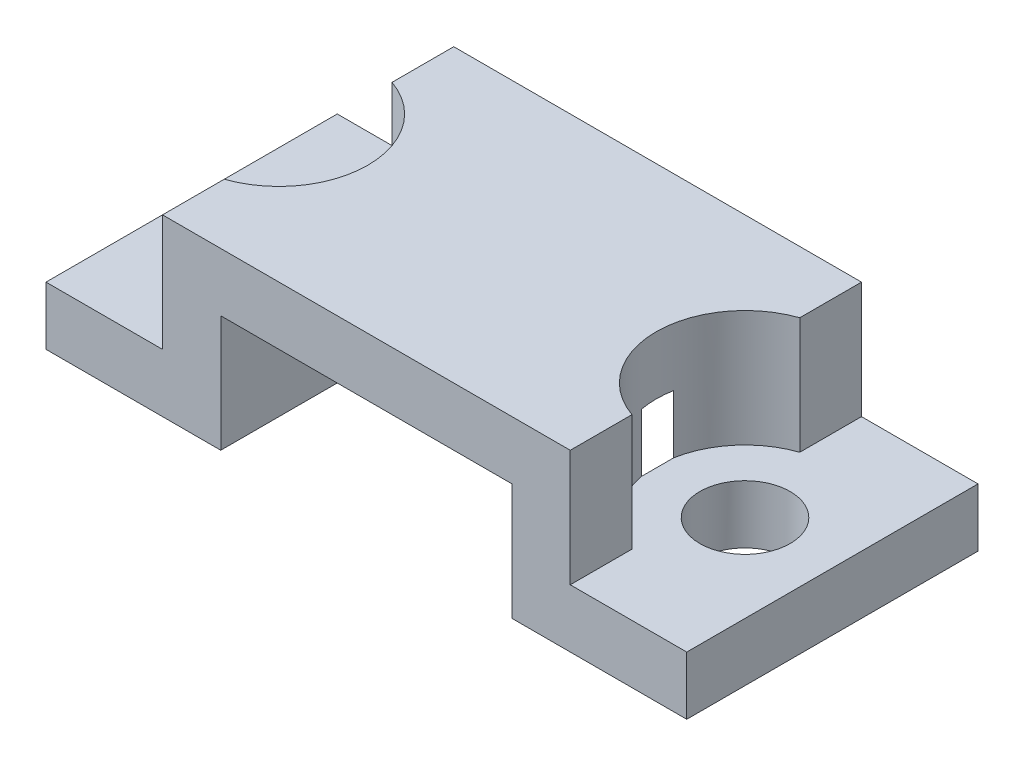
SolidWorks part; units mm, degrees
ref_plane "前视基准面" through (0, 0, 0) normal (0, 0, 1) x (1, 0, 0)
ref_plane "上视基准面" through (0, 0, 0) normal (0, 1, 0) x (1, 0, 0)
ref_plane "右视基准面" through (0, 0, 0) normal (1, 0, 0) x (0, 0, -1)
sketch "草图1" plane through (0, 0, 0) normal (0, 1, 0) x (1, 0, 0)
  line L1 (-11, -5) -> (11, -5)
  line L2 (-11, -5) -> (-11, 5)
  line L3 (-11, 5) -> (11, 5)
  line L4 (11, -5) -> (11, 5)
  line L5 (-11, -5) -> (11, 5) construction
  line L6 (-11, 5) -> (11, -5) construction
  point P0 (0, 0)
  dimension "D1" = 10
  dimension "D2" = 22
extrude "凸台-拉伸1" add sketch "草图1" along normal blind 6
sketch "草图2" plane through (0, 0, 5) normal (0, 0, 1) x (1, 0, 0)
  line L1 (-5, 0) -> (5, 0)
  line L2 (-5, 0) -> (-5, 4)
  line L3 (-5, 4) -> (5, 4)
  line L4 (-11, 0) -> (11, 0)
  line L5 (11, 0) -> (11, 6)
  line L6 (11, 6) -> (-11, 6)
  line L7 (-11, 6) -> (-11, 0)
  line L8 (-11, 0) -> (11, 0)
  line L9 (11, 0) -> (11, 6)
  line L10 (11, 6) -> (-11, 6)
  line L11 (-11, 6) -> (-11, 0)
  line L12 (5, 0) -> (5, 4)
  line L13 (-11, 0) -> (-5, 0)
  line L14 (-11, 0) -> (-11, 2)
  line L15 (-11, 2) -> (-5, 2)
  line L16 (-5, 0) -> (-5, 2)
  line L17 (11, 0) -> (5, 0)
  line L18 (11, 0) -> (11, 2)
  line L19 (11, 2) -> (5, 2)
  line L20 (5, 0) -> (5, 2)
  line L21 (-11, 6) -> (-7, 6)
  line L22 (-11, 6) -> (-11, 2)
  line L23 (-11, 2) -> (-7, 2)
  line L24 (-7, 6) -> (-7, 2)
  line L25 (11, 6) -> (7, 6)
  line L26 (11, 6) -> (11, 2)
  line L27 (11, 2) -> (7, 2)
  line L28 (7, 6) -> (7, 2)
  line M13 (-11, 0) -> (11, 0)
  line M15 (11, 6) -> (-11, 6)
  line M16 (-11, 6) -> (-11, 0)
  dimension "D2" = 10
  dimension "D3" = 6
  dimension "D4" = 2
  dimension "D5" = 2
  dimension "D6" = 2
  dimension "D7" = 2
  dimension "D8" = 2
  dimension "D1" = 0
extrude "切除-拉伸1" cut sketch "草图2" against normal blind 24 contours L24 L10 L15 M16 | L28 L19 L9 M15 | L12 L3 L2 M13 region at (0, 2, 5) region at (-9, 4, 5) region at (9, 4, 5)
sketch "草图3" plane through (0, 2, 0) normal (0, 1, 0) x (1, 0, 0)
  line L4 (-11, 5) -> (-11, -5)
  line L5 (-11, -5) -> (-7, -5)
  line L6 (-7, -5) -> (-7, 5)
  line L7 (-7, 5) -> (-11, 5)
  line L8 (-11, 5) -> (-11, -5)
  line L9 (-11, -5) -> (-7, -5)
  line L10 (-7, -5) -> (-7, 5)
  line L11 (-7, 5) -> (-11, 5)
  line L12 (11, 5) -> (7, 5)
  line L13 (7, 5) -> (7, -5)
  line L14 (7, -5) -> (11, -5)
  line L15 (11, -5) -> (11, 5)
  line L16 (11, 5) -> (7, 5)
  line L17 (7, 5) -> (7, -5)
  line L18 (7, -5) -> (11, -5)
  line L19 (11, -5) -> (11, 5)
  circle A0 centre (-8, 0) radius 1.55
  circle A1 centre (8, 0) radius 1.55
  circle A2 centre (-8, 0) radius 3.05
  circle A3 centre (8, 0) radius 3.05
  dimension "D3" = 3.1
  dimension "D4" = 3.1
  dimension "D5" = 3
  dimension "D6" = 3
  dimension "D1" = 0
  dimension "D2" = 0
  dimension "D7" = 1.5
extrude "切除-拉伸2" cut sketch "草图3" against normal blind 6 contours A1 | A0
extrude "切除-拉伸3" cut sketch "草图3<3>" along normal blind 6 contours A2 | A3
sketch "草图3<3>" plane through (0, 2, 0) normal (0, 1, 0) x (1, 0, 0) same geometry as "草图3"
